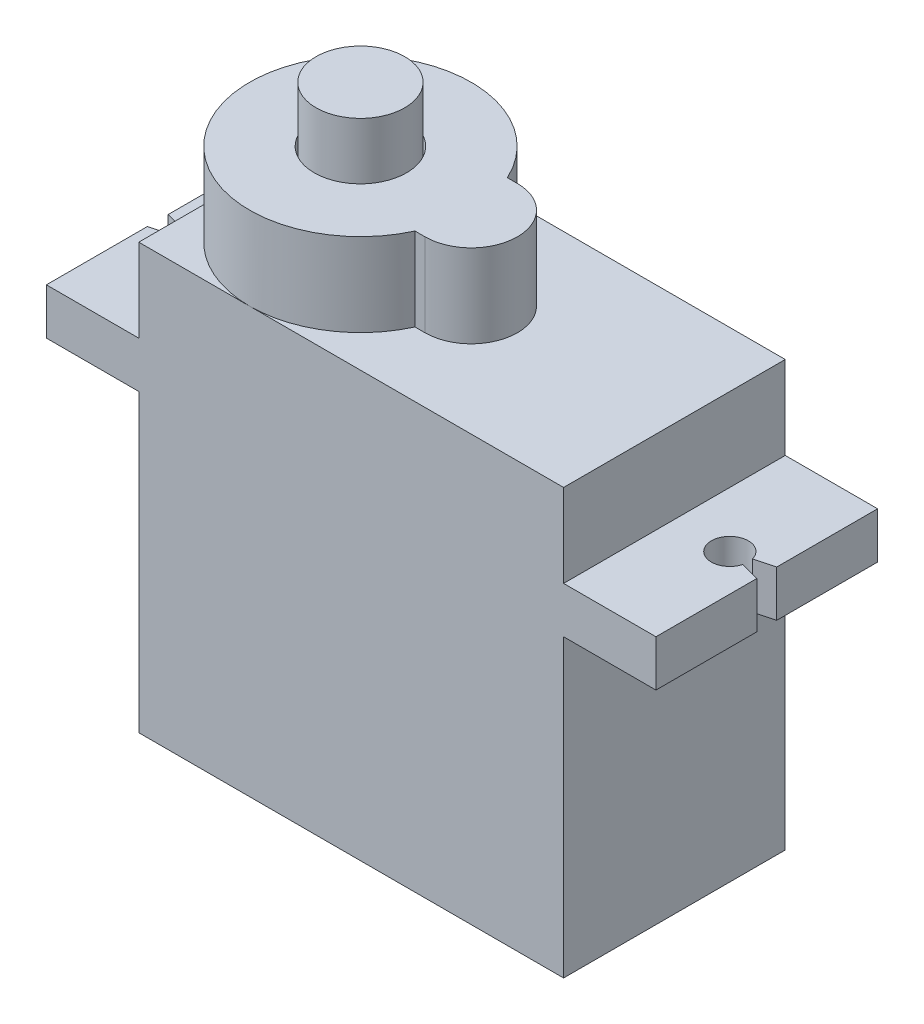
SolidWorks part; units mm, degrees
material "acrilico"
ref_plane "Alzado" through (0, 0, 0) normal (0, 0, 1) x (1, 0, 0)
ref_plane "Planta" through (0, 0, 0) normal (0, 1, 0) x (1, 0, 0)
ref_plane "Vista lateral" through (0, 0, 0) normal (1, 0, 0) x (0, 0, -1)
sketch "Croquis1" plane through (0, 0, 0) normal (0, 0, 1) x (1, 0, 0)
  line L0 (-11.5, 7) -> (-16.5, 7)
  line L1 (-11.5, -11.5) -> (11.5, -11.5)
  line L2 (-11.5, -11.5) -> (-11.5, 4.5)
  line L3 (-11.5, 11.5) -> (11.5, 11.5)
  line L4 (11.5, -11.5) -> (11.5, 4.5)
  line L5 (-11.5, -11.5) -> (11.5, 11.5) construction
  line L6 (-11.5, 11.5) -> (11.5, -11.5) construction
  line L7 (11.5, 7) -> (16.5, 7)
  line L8 (16.5, 7) -> (16.5, 4.5)
  line L9 (16.5, 4.5) -> (11.5, 4.5)
  line L10 (-16.5, 7) -> (-16.5, 4.5)
  line L11 (-16.5, 4.5) -> (-11.5, 4.5)
  line L12 (-11.5, 7) -> (-11.5, 11.5)
  line L13 (11.5, 7) -> (11.5, 11.5)
  point P0 (0, 0)
  dimension "D1" = 23
  dimension "D2" = 23
  dimension "D3" = 5
  dimension "D4" = 2.5
  dimension "D5" = 5
  dimension "D6" = 2.5
  dimension "D7" = 4.5
extrude "Saliente-Extruir1" add sketch "Croquis1" along normal blind 6 and the other way blind 6
sketch "Croquis3" plane through (0, 11.5, 0) normal (0, 1, 0) x (1, 0, 0)
  line L0 (0.5, 2.5) -> (-0.0456, 2.5)
  line L1 (0.5, -2.5) -> (-0.0456, -2.5)
  arc A0 (-0.0456, 2.5) -> (-0.0456, -2.5) centre (-5.5, 0) ccw
  arc A1 (0.5, -2.5) -> (0.5, 2.5) centre (0.5, 0) ccw
  circle A2 centre (-5.5, 0) radius 2.5
extrude "Saliente-Extruir2" add sketch "Croquis3" along normal blind 4.5
sketch "Croquis4" plane through (0, 11.5, 0) normal (0, 1, 0) x (1, 0, 0)
  circle A0 centre (-5.5, 0) radius 2.4
extrude "Saliente-Extruir5" add sketch "Croquis4" along normal blind 7.5 contours A0
sketch "Croquis6" plane through (0, 7, 0) normal (0, 1, 0) x (1, 0, 0)
  line L0 (-16.5, 0.5925) -> (-16.5, -0.5359)
  line L1 (-16.5, 6) -> (-16.5, -6) construction
  line L3 (16.5, 6) -> (16.5, -6) construction
  line L4 (-11.5, 0) -> (-13.4916, 0) construction
  line L5 (-11.5, 6) -> (-11.5, -6) construction
  line L6 (11.5, 0) -> (13.5, 0) construction
  line L7 (11.5, 6) -> (11.5, -6) construction
  line L9 (15.4659, 0.2588) -> (16.5, 0.5359)
  line L10 (-15.434, -0.2503) -> (-16.5, -0.5359)
  line L11 (-15.4599, 0.3138) -> (-16.5, 0.5925)
  line L12 (16.5, 0.5359) -> (16.5, -0.5359)
  line L13 (16.5, -0.5359) -> (15.4659, -0.2588)
  arc A0 (-15.434, -0.2503) -> (-15.4599, 0.3138) centre (-14.4887, 0.0758) ccw
  arc A1 (15.4659, 0.2588) -> (15.4659, -0.2588) centre (14.5, 0) ccw
extrude "Cortar-Extruir1" cut sketch "Croquis6" against normal blind 3.5
